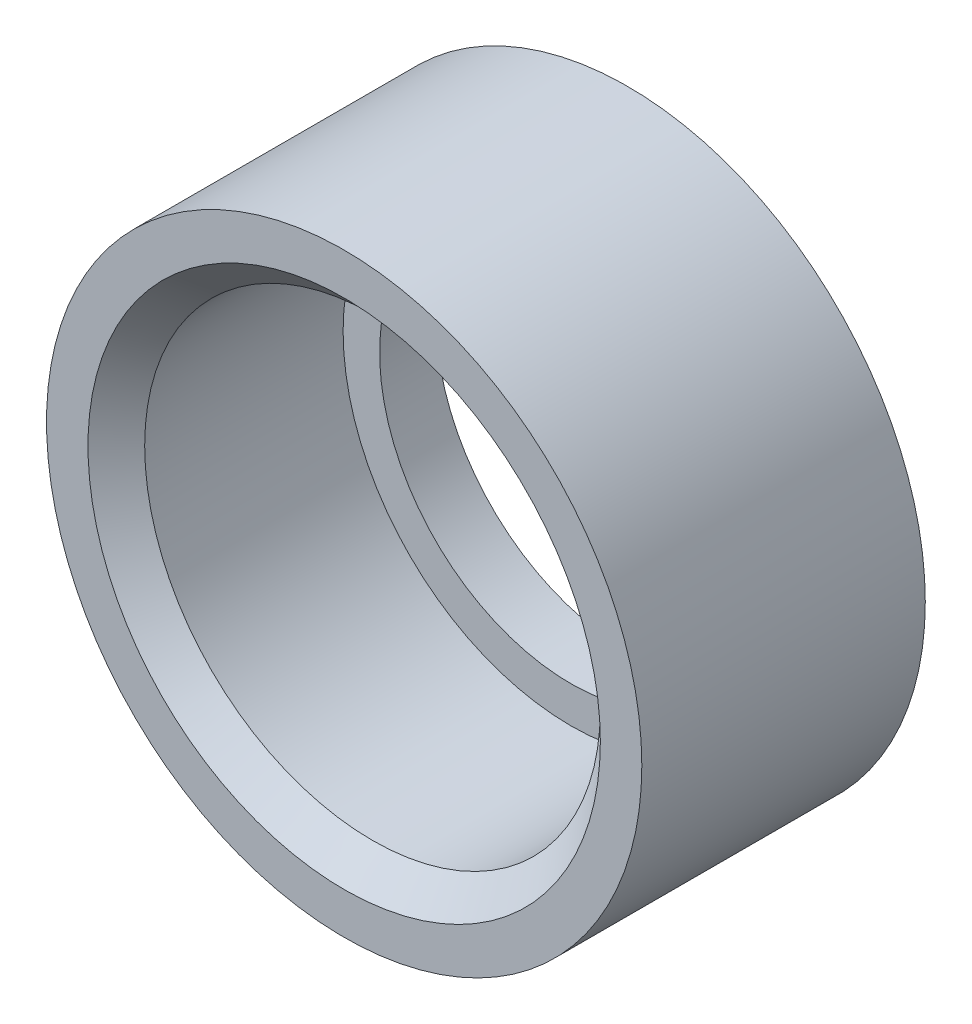
SolidWorks part; units mm, degrees
material "ABS"
ref_plane "Front Plane" through (0, 0, 0) normal (0, 0, 1) x (1, 0, 0)
ref_plane "Top Plane" through (0, 0, 0) normal (0, 1, 0) x (1, 0, 0)
ref_plane "Right Plane" through (0, 0, 0) normal (1, 0, 0) x (0, 0, -1)
sketch "Sketch1" plane through (0, 0, 0) normal (0, 0, 1) x (1, 0, 0)
  circle A0 centre (0, 0) radius 10.5
  circle A1 centre (0, 0) radius 8.0375
  circle A2 centre (0, 0) radius 6.75
  dimension "D1" = 16.075
  dimension "D2" = 21
  dimension "D3" = 13.5
extrude "Boss-Extrude1" add sketch "Sketch1" along normal mid plane 10 contours A0 A1 region at (-10.203, 0, 0)
extrude "Boss-Extrude2" add sketch "Sketch1<3>" along normal blind 2 from surface contours A1 A2 region at (-7.8102, 0, 0) starting at face at (8.0375, 0, -5)
sketch "Sketch1<3>" plane through (0, 0, 0) normal (0, 0, 1) x (1, 0, 0) same geometry as "Sketch1"
chamfer "Chamfer1" distance 1 angle 45 1 edges at (8.0375, 0, 5)
